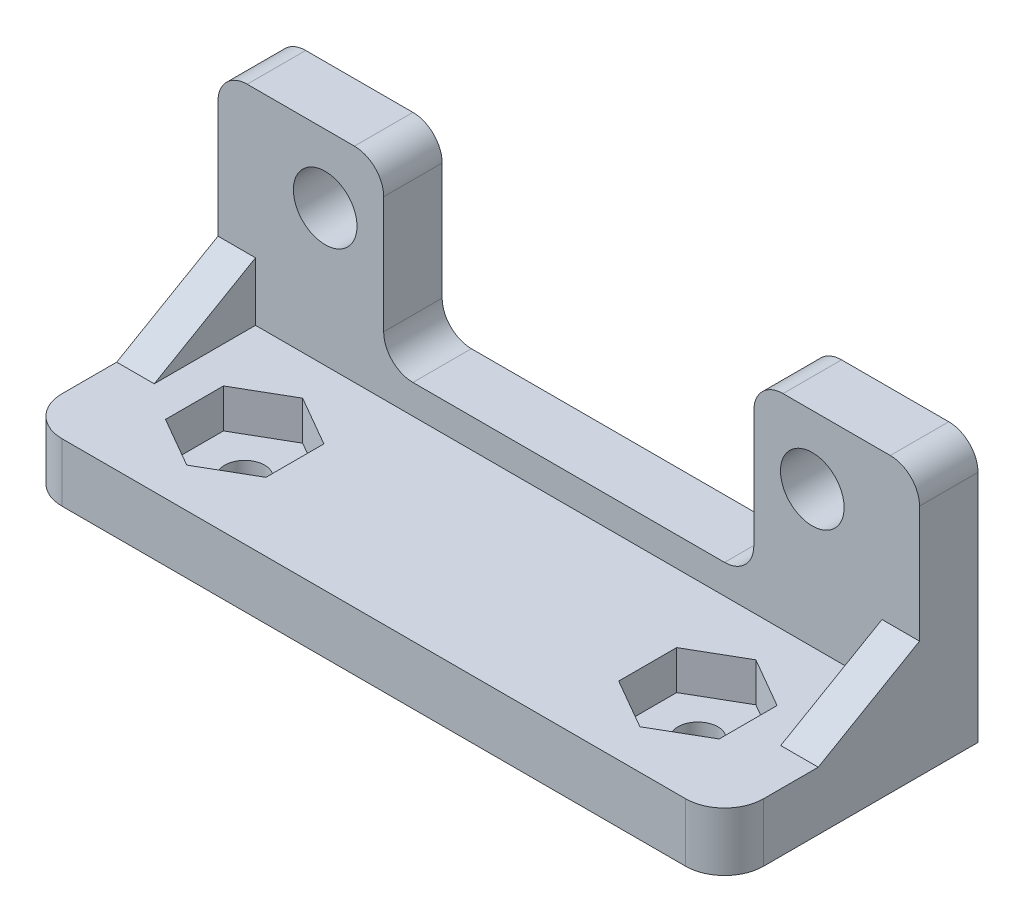
SolidWorks part; units mm, degrees
material "ABS"
ref_plane "Front Plane" through (0, 0, 0) normal (0, 0, 1) x (1, 0, 0)
ref_plane "Top Plane" through (0, 0, 0) normal (0, 1, 0) x (1, 0, 0)
ref_plane "Right Plane" through (0, 0, 0) normal (1, 0, 0) x (0, 0, -1)
sketch "Sketch1" plane through (0, 0, 0) normal (0, 0, 1) x (1, 0, 0)
  line L0 (-17.995, 0) -> (17.995, 0) construction
  line L3 (-17.995, 0) -> (-17.995, -10)
  line L4 (-17.995, -10) -> (17.995, -10)
  line L5 (17.995, 0) -> (17.995, -10)
  line L6 (-9.495, 0) -> (-9.495, -5.5)
  line L7 (-9.495, -5.5) -> (9.495, -5.5)
  line L8 (9.495, -5.5) -> (9.495, 0)
  line L9 (-17.995, 0) -> (-17.995, 3.5)
  line L10 (-17.995, 3.5) -> (-9.495, 3.5)
  line L11 (-9.495, 3.5) -> (-9.495, 0)
  line L12 (9.495, 0) -> (9.495, 3.5)
  line L13 (9.495, 3.5) -> (17.995, 3.5)
  line L14 (17.995, 3.5) -> (17.995, 0)
  point P0 (-12.495, 0)
  point P4 (0, 0)
  point P6 (12.495, 0)
  point P11 (0, 0)
  dimension "D2" = 3
  dimension "D3" = 3
  dimension "D1" = 8.5
  dimension "D4" = 5.5
  dimension "D5" = 10
  dimension "D6" = 8.5
  dimension "D7" = 24.99
  dimension "D8" = 3.5
extrude "Boss-Extrude1" add sketch "Sketch1" along normal blind 3 contours L14 L5 L4 L3 L9 L10 L11 L6 L7 L8 L12 L13
sketch "Sketch2" plane through (0, 0, 0) normal (0, 0, 1) x (1, 0, 0)
  line L0 (-17.995, 3.5) -> (-17.995, -10) construction
  line L1 (-17.995, -10) -> (17.995, -10)
  line L2 (-17.995, -10) -> (-17.995, -7)
  line L3 (-17.995, -7) -> (17.995, -7)
  line L4 (17.995, -10) -> (17.995, -7)
  point P4 (-15.8295, -10)
  point P6 (0, -7)
  point P8 (-15.8295, -6.2638)
  point P9 (-15.8295, -10)
  dimension "D1" = 3
extrude "Boss-Extrude2" add sketch "Sketch2" along normal blind 13
sketch "Sketch3" plane through (0, -7, 0) normal (0, 1, 0) x (1, 0, 0)
  line L0 (-11.625, -8) -> (11.625, -8) construction
  line L1 (17.995, -13) -> (-17.995, -13) construction
  point P2 (0, -8)
  point P6 (-12.5, -8)
  dimension "D1" = 23.25
  dimension "D2" = 5
sketch "Sketch4" plane through (0, 0, 0) normal (0, 0, -1) x (-1, 0, 0)
  point P0 (12.495, 0)
  point P3 (-12.495, 0)
  point P6 (12.5, 0)
  point P7 (10.8295, 0)
  point P9 (0, 0)
  point P10 (-10.8295, 0)
hole_wizard "#4 Clearance Hole1" positions "Sketch4" profile "Sketch5" hole size "#4" standard "ANSI Inch" end condition through all
sketch "Sketch5" plane through (-12.495, 0, 0) normal (1, 0, 0) x (0, 1, 0)
  line L0 (0, 0) -> (0, 13)
  line L1 (0, 13) -> (1.6319, 13)
  line L2 (1.6319, 13) -> (1.6319, 0)
  line L5 (1.6319, 0) -> (0, 0)
  line L11 (0, -6.35) -> (0, 107.95) construction
  dimension "Thru Hole Dia." = 3.2639
  dimension "Thru Hole Depth" = 13
sketch "Sketch6" plane through (0, -7, 0) normal (0, 1, 0) x (1, 0, 0)
  point P0 (-11.625, -8)
  point P3 (11.625, -8)
hole_wizard "M2.5x0.45 Tapped Hole1" positions "Sketch6" profile "Sketch7" tap size "M2.5x0.45" standard "ANSI Metric" end condition through all
sketch "Sketch7" plane through (-11.625, -7, 8) normal (1, 0, 0) x (0, 0, 1)
  line L0 (0, 0) -> (0, 3)
  line L1 (0, 3) -> (1.025, 3)
  line L2 (1.025, 3) -> (1.025, 0)
  line L5 (1.025, 0) -> (0, 0)
  line L11 (0, -6.35) -> (0, 107.95) construction
  dimension "Thru Tap Drill Dia." = 2.05
  dimension "Thru Tap Drill Depth" = 3
sketch "Sketch9" plane through (0, -7, 0) normal (0, 1, 0) x (1, 0, 0)
  line L1 (-9.05, -6.5133) -> (-11.625, -5.0266)
  line L2 (-11.625, -5.0266) -> (-14.2, -6.5133)
  line L3 (-14.2, -6.5133) -> (-14.2, -9.4867)
  line L4 (-14.2, -9.4867) -> (-11.625, -10.9734)
  line L5 (-11.625, -10.9734) -> (-9.05, -9.4867)
  line L6 (-9.05, -9.4867) -> (-9.05, -6.5133)
  line L8 (11.625, -5.0266) -> (9.05, -6.5133)
  line L9 (9.05, -6.5133) -> (9.05, -9.4867)
  line L10 (9.05, -9.4867) -> (11.625, -10.9734)
  line L11 (11.625, -10.9734) -> (14.2, -9.4867)
  line L12 (14.2, -9.4867) -> (14.2, -6.5133)
  line L13 (14.2, -6.5133) -> (11.625, -5.0266)
  circle A0 centre (-11.625, -8) radius 2.575 construction
  circle A1 centre (11.625, -8) radius 2.575 construction
  dimension "D1" = 5.15
extrude "Cut-Extrude1" cut sketch "Sketch9" against normal blind 2 and the other way through all
fillet "Fillet1" radius 2 2 edges at (17.995, -8.5, 13) (-17.995, -8.5, 13)
sketch "Sketch8" plane through (-17.995, 0, 0) normal (-1, 0, 0) x (0, 0, 1)
  line L0 (3, -4) -> (8.1962, -7)
  line L2 (3, -7) -> (11, -7) construction
  line L3 (3, 3.5) -> (3, -7) construction
  point P2 (3, -4)
  point P6 (8.1962, -7)
  point P7 (0, 0)
  dimension "D1" = 30
  dimension "D2" = 3
rib "Rib1" sketch "Sketch8" sketch "Sketch8" thickness 1.925 extrusion direction parallel to sketch draft on no parameters "D1"=1.925
mirror "Mirror1" about plane through (0, 0, 0) normal (1, 0, 0) of "Rib1"
fillet "Fillet2" radius 1.5 6 edges at (17.995, 3.5, 1.5) (9.495, 3.5, 1.5) (9.495, -5.5, 1.5) (-17.995, 3.5, 1.5) (-9.495, 3.5, 1.5) (-9.495, -5.5, 1.5)
